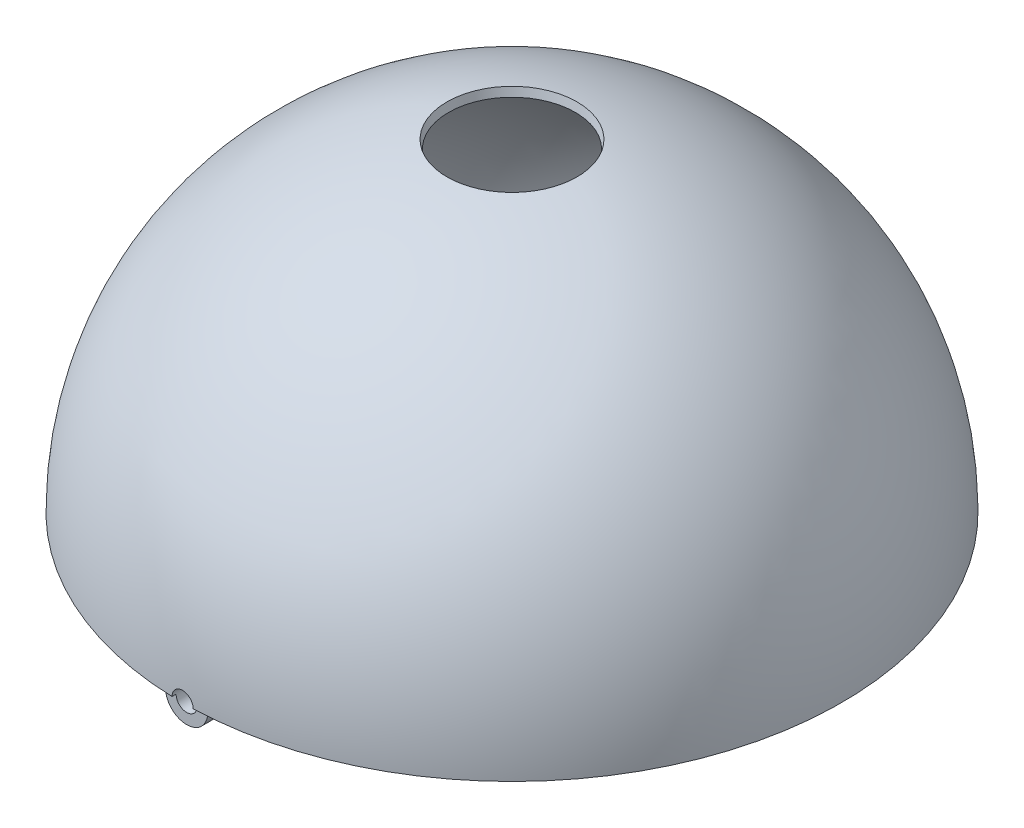
SolidWorks part; units mm, degrees
ref_plane "Front Plane" through (0, 0, 0) normal (0, 0, 1) x (1, 0, 0)
ref_plane "Top Plane" through (0, 0, 0) normal (0, 1, 0) x (1, 0, 0)
ref_plane "Right Plane" through (0, 0, 0) normal (1, 0, 0) x (0, 0, -1)
sketch "Sketch1" plane through (0, 0, 0) normal (0, 0, 1) x (1, 0, 0)
  line L0 (0, 0) -> (0, 78) construction
  line L1 (-78, 0) -> (-76, 0)
  line L2 (76, 0) -> (78, 0)
  line L3 (-15.3947, 76.4657) -> (-15, 74.505)
  arc A0 (-15.3947, 76.4657) -> (-78, 0) centre (0, 0) ccw
  arc A1 (-15, 74.505) -> (-76, 0) centre (0, 0) ccw
  dimension "D1" = 78
  dimension "D2" = 2
  dimension "D3" = 15
revolve "Revolve1" add sketch "Sketch1" angle 360 about L0
ref_plane "Plane1" through (0, 0, 77) normal (0, 0, 1) x (1, 0, 0)
sketch "Sketch2" plane through (0, 0, 77) normal (0, 0, 1) x (1, 0, 0)
  circle A0 centre (0, 0) radius 5
  dimension "D1" = 10
extrude "Boss-Extrude1" add sketch "Sketch2" against normal blind 10 contours A0
ref_plane "Plane3" through (0, 0, -78) normal (0, 0, 1) x (1, 0, 0)
sketch "Sketch3" plane through (0, 0, 0) normal (0, 0, 1) x (1, 0, 0)
  line L0 (-30.7, 59.6911) -> (-30.7, 69.6911)
  line L1 (-30.7, 59.6911) -> (-47.7, 59.6911)
  arc A0 (-30.7, 69.6911) -> (-47.7, 59.6911) centre (-0.481, -1.1313) ccw
  point P5 (-46.9793, 59.6911)
  point P6 (0, 0)
  point P7 (-30.7, 69.5842)
  point P8 (-46.2739, 59.6911)
  point P9 (0, 0)
  point P10 (-46.1655, 60.4378)
  point P11 (0, 0)
  point P12 (-30.7, 69.5312)
  dimension "D1" = 77
  dimension "D2" = 10
  dimension "D3" = 17
ref_axis "Axis1" through (0, 76.4657, 0) along (0, -1, 0)
revolve "Revolve2" add sketch "Sketch3" angle 360 about axis through (0, 76.4657, 0) along (0, -1, 0)
sketch "Sketch4" plane through (0, 59.6911, 0) normal (0, -1, 0) x (1, 0, 0)
  line L0 (-30.7, -19.275) -> (5, -19.275) construction
  line L2 (-30.7, 19.275) -> (-30.7, -19.275)
  line L4 (-23.8949, 19.275) -> (-23.8949, -19.275)
  circle A0 centre (0, 0) radius 30.7 construction
  circle A1 centre (-34.1, 3.2) radius 1.4
  circle A2 centre (-34.1, -3.2) radius 1.4
  arc A3 (-30.7, 19.275) -> (-30.7, -19.275) centre (0, 0) cw
  arc A4 (-23.8949, 19.275) -> (-23.8949, -19.275) centre (0, 0) cw
  point P16 (0, 0)
  dimension "D1" = 2.8
  dimension "D2" = 2.8
extrude "Cut-Extrude1" cut sketch "Sketch4" against normal blind 5
mirror "Mirror1" about plane through (0, 0, 0) normal (0, 0, 1) of "Boss-Extrude1"
sketch "Sketch5" plane through (0, 0, 67) normal (0, 0, -1) x (-1, 0, 0)
  circle A0 centre (0, 0) radius 2.45
  dimension "D1" = 4.9
extrude "Cut-Extrude2" cut sketch "Sketch5" against normal blind 3
ref_plane "Plane4" through (0, 0, 72) normal (0, 0, -1) x (-1, 0, 0)
sketch "Sketch6" plane through (0, 0, 72) normal (0, 0, -1) x (-1, 0, 0)
  circle A0 centre (0, 0) radius 2.5
  dimension "D1" = 5
sketch "Sketch7" plane through (0, 0, 70) normal (0, 0, -1) x (-1, 0, 0)
  circle A0 centre (0, 0) radius 1
  dimension "D1" = 2
extrude "Cut-Extrude3" cut sketch "Sketch6" against normal blind 13
extrude "Cut-Extrude4" cut sketch "Sketch7" against normal blind 13
